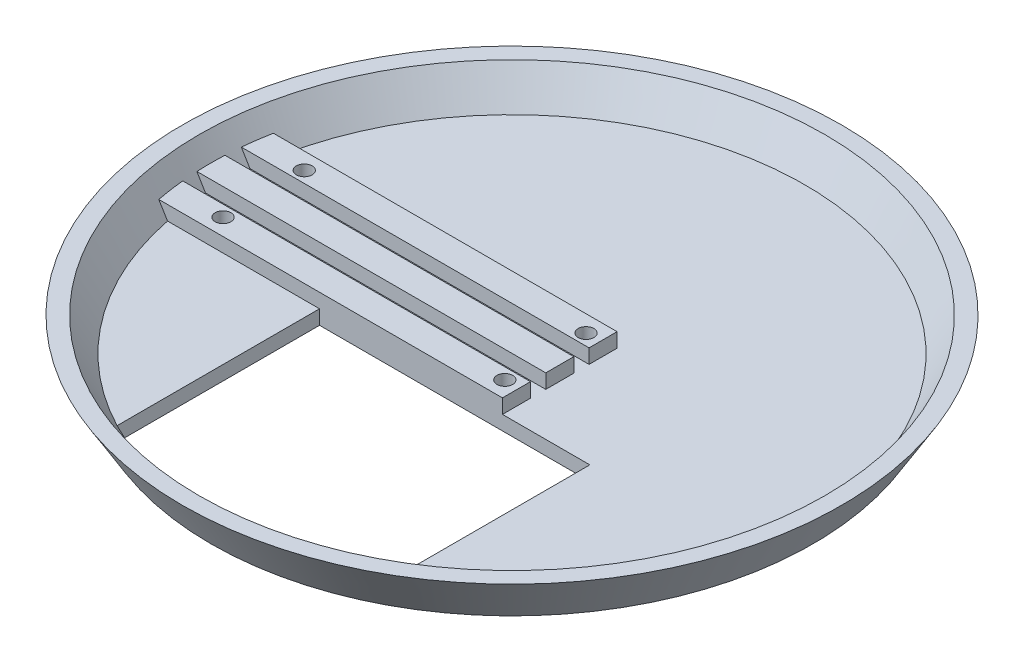
SolidWorks part; units mm, degrees
ref_plane "Front Plane" through (0, 0, 0) normal (0, 0, 1) x (1, 0, 0)
ref_plane "Top Plane" through (0, 0, 0) normal (0, 1, 0) x (1, 0, 0)
ref_plane "Right Plane" through (0, 0, 0) normal (1, 0, 0) x (0, 0, -1)
sketch "Sketch1" plane through (0, 0, 0) normal (0, 0, 1) x (1, 0, 0)
  line L0 (0, 0) -> (63, 0)
  line L1 (63, 0) -> (69, 10)
  line L6 (0, 3) -> (61.3014, 3)
  line L7 (61.3014, 3) -> (65.5014, 10)
  line L8 (69, 10) -> (65.5014, 10)
  line L9 (0, 0) -> (0, 3)
  line L10 (61.3014, 3) -> (66.4275, 11.5435) construction
  dimension "D1" = 69
  dimension "D2" = 63
  dimension "D3" = 10
  dimension "D4" = 3
revolve "Revolve1" add sketch "Sketch1" angle 360 about L9
sketch "Sketch2" plane through (0, 3, 0) normal (0, 1, 0) x (1, 0, 0)
  line L0 (-28.3, -12) -> (-28.3, -54.3781)
  line L1 (-28.3, -12) -> (28.3, -12)
  line L5 (28.3, -12) -> (28.3, -54.3781)
  arc A0 (-28.3, -54.3781) -> (28.3, -54.3781) centre (0, 0) ccw
  circle A3 centre (0, 0) radius 61.3014 construction
  dimension "D2" = 28.3
  dimension "D1" = 56.6
  dimension "D4" = 12
extrude "Cut-Extrude1" cut sketch "Sketch2" against normal through all
sketch "Sketch4" plane through (0, 0, 0) normal (1, 0, 0) x (0, 0, -1)
  line L0 (-6.1333, 3) -> (-12, 3)
  line L5 (-12, 3) -> (-12, 6)
  line L6 (-12, 6) -> (-6.1333, 6)
  line L7 (-6.1333, 6) -> (-6.1333, 3)
  line L8 (-2.9333, 3) -> (2.9333, 3)
  line L9 (2.9333, 3) -> (2.9333, 6)
  line L10 (2.9333, 6) -> (-2.9333, 6)
  line L11 (-2.9333, 6) -> (-2.9333, 3)
  line L12 (12, 3) -> (6.1333, 3)
  line L13 (6.1333, 3) -> (6.1333, 6)
  line L14 (6.1333, 6) -> (12, 6)
  line L15 (12, 6) -> (12, 3)
  point P13 (0, 3)
  dimension "D1" = 12
  dimension "D2" = 3
  dimension "D3" = 3
  dimension "D4" = 3.2
  dimension "D5" = 3.2
  dimension "D6" = 12
extrude "Boss-Extrude1" add sketch "Sketch4" along normal blind 10 and the other way blind 63.5
sketch "Sketch5" plane through (0, 0, 0) normal (0, 1, 0) x (1, 0, 0)
  line L0 (10, 2.9333) -> (10, -2.9333) construction
  circle A0 centre (7, -8.5) radius 1.65
  circle A1 centre (7, 0) radius 1.65
  circle A2 centre (7, 8.5) radius 1.65
  circle A6 centre (-52, 8.5) radius 1.65
  circle A8 centre (-52, -8.5) radius 1.65
  circle A9 centre (-22.5, 0) radius 1.65 [skipped]
  circle A10 centre (-52, 0) radius 1.65 [skipped]
  circle A11 centre (-22.5, 8.5) radius 1.65 [skipped]
  circle A12 centre (-22.5, -8.5) radius 1.65 [skipped]
  point P6 (7, 0)
  point P8 (0, 0)
  dimension "D2" = 3.3
  dimension "D3" = 8.5
  dimension "D6" = 3
  dimension "D7" = 59
  dimension "D4" = 8.5
  dimension "D5" = 3
extrude "Cut-Extrude2" cut sketch "Sketch5" along normal through all contours A2 | A0 | A8 | A6
